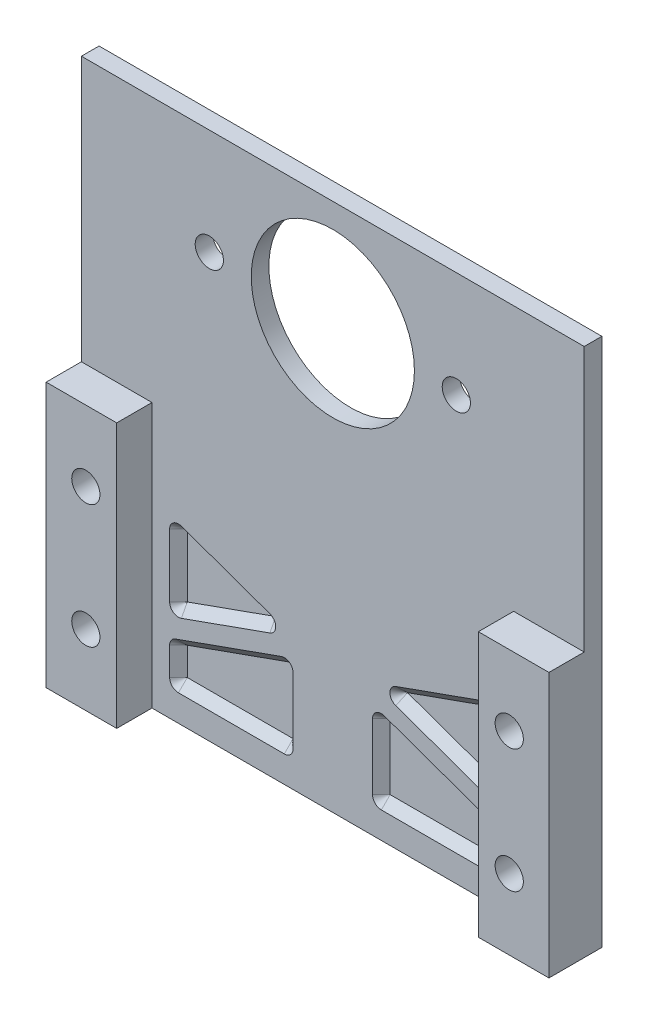
SolidWorks part; units mm, degrees
ref_plane "Ebene vorne" through (0, 0, 0) normal (0, 0, 1) x (1, 0, 0)
ref_plane "Ebene oben" through (0, 0, 0) normal (0, 1, 0) x (1, 0, 0)
ref_plane "Ebene rechts" through (0, 0, 0) normal (1, 0, 0) x (0, 0, -1)
sketch "Skizze1" plane through (0, 0, 0) normal (0, 0, 1) x (1, 0, 0)
  line L0 (0, 0) -> (0, 60) construction
  line L1 (28.5, 0) -> (-28.5, 0)
  line L2 (-28.5, 0) -> (-28.5, 60)
  line L3 (-28.5, 60) -> (28.5, 60)
  line L4 (28.5, 0) -> (28.5, 60)
  dimension "D1" = 57
  dimension "D2" = 60
extrude "Grundplatte" add sketch "Skizze1" along normal blind 2
sketch "Skizze2" plane through (0, 0, 2) normal (0, 0, 1) x (1, 0, 0)
  line L0 (0, 0) -> (0, 48) construction
  line L1 (14, 48) -> (-14, 48) construction
  line L2 (28.5, 60) -> (-28.5, 60) construction
  circle A0 centre (0, 48) radius 9.25
  circle A1 centre (-14, 48) radius 1.6
  circle A2 centre (14, 48) radius 1.6
  dimension "D2" = 18.5
  dimension "D3" = 3.2
  dimension "D1" = 12
  dimension "D4" = 28
extrude "Ausschnitt_Rolle" cut sketch "Skizze2" against normal through all
sketch "Skizze4" plane through (0, 0, 2) normal (0, 0, 1) x (1, 0, 0)
  line L0 (0, 60) -> (0, 0) construction
  line L1 (28.5, 60) -> (-28.5, 60) construction
  line L2 (20.5, 0) -> (20.5, 30)
  line L3 (-28.5, 0) -> (-20.5, 0)
  line L4 (-28.5, 0) -> (-28.5, 30)
  line L5 (-28.5, 30) -> (-20.5, 30)
  line L6 (-20.5, 0) -> (-20.5, 30)
  line L7 (28.5, 30) -> (20.5, 30)
  line L8 (28.5, 0) -> (28.5, 30)
  line L9 (28.5, 0) -> (20.5, 0)
  dimension "D1" = 8
  dimension "D2" = 30
extrude "Aufsatz Getriebe" add sketch "Skizze4" along normal blind 4
sketch "Skizze3" plane through (0, 0, 2) normal (0, 0, 1) x (1, 0, 0)
  line L0 (-24, 22) -> (-24, 8) construction
  line L1 (-24, 15) -> (24, 15) construction
  line L2 (0, 15) -> (0, 0) construction
  line L3 (-20.5, 0) -> (20.5, 0) construction
  line L4 (24, 22) -> (24, 8) construction
  line L5 (-20.5, 15) -> (-24, 15) construction
  line L6 (-20.5, 0) -> (-20.5, 30) construction
  circle A0 centre (-24, 22) radius 1.6
  circle A1 centre (-24, 8) radius 1.6
  circle A2 centre (24, 8) radius 1.6
  circle A3 centre (24, 22) radius 1.6
  dimension "D1" = 3.2
  dimension "D2" = 14
  dimension "D4" = 48
extrude "Bohrungen Getriebe" cut sketch "Skizze3" against normal through all from surface starting at face at (-24.5, 15, 6)
sketch "Skizze5" plane through (0, 0, 2) normal (0, 0, 1) x (1, 0, 0)
  line L0 (0, 60) -> (0, 0) construction
  line L1 (28.5, 60) -> (-28.5, 60) construction
  line L2 (-18.5, 20) -> (-18.5, 10)
  line L3 (-18.5, 10) -> (-4.5, 15)
  line L4 (-4.5, 15) -> (-18.5, 20)
  line L5 (-20.5, 15) -> (-18.5, 15) construction
  line L6 (-20.5, 0) -> (-20.5, 30) construction
  line L7 (-18.5, 15) -> (-4.5, 15) construction
  line L8 (-18.5, 7.8763) -> (-18.5, 3)
  line L9 (-18.5, 3) -> (-4.5, 3)
  line L10 (-4.5, 3) -> (-4.5, 12.8763)
  line L11 (-4.5, 12.8763) -> (-18.5, 7.8763)
  line L12 (-20.5, 0) -> (20.5, 0) construction
  line L13 (-20.5, 0) -> (-20.5, 30) construction
  line L14 (18.5, 15) -> (4.5, 15) construction
  line L15 (20.5, 15) -> (18.5, 15) construction
  line L16 (4.5, 12.8763) -> (18.5, 7.8763)
  line L17 (4.5, 3) -> (4.5, 12.8763)
  line L18 (18.5, 3) -> (4.5, 3)
  line L19 (18.5, 7.8763) -> (18.5, 3)
  line L20 (4.5, 15) -> (18.5, 20)
  line L21 (18.5, 10) -> (4.5, 15)
  line L22 (18.5, 20) -> (18.5, 10)
  dimension "D1" = 10
  dimension "D2" = 14
  dimension "D3" = 2
  dimension "D4" = 3
  dimension "D5" = 2
extrude "Schnitt-Linear austragen3" cut sketch "Skizze5" against normal offset from surface (1 mm away) 1 up to face at (22.4, 22, 0)
fillet "Verrundung1" radius 1 14 edges at (18.5, 20, 1.5) (18.5, 10, 1.5) (4.5, 15, 1.5) (4.5, 3, 1.5) (4.5, 12.8763, 1.5) (18.5, 7.8763, 1.5) (18.5, 3, 1.5) (-4.5, 3, 1.5) (-4.5, 12.8763, 1.5) (-4.5, 15, 1.5) (-18.5, 7.8763, 1.5) (-18.5, 3, 1.5) (-18.5, 10, 1.5) (-18.5, 20, 1.5)
chamfer "Fase1" distance 1 angle 45 28 edges at (4.924, 12.2747, 1) (11.8363, 10.2562, 1) (18.3174, 7.7476, 1) (18.5, 5.5858, 1) (18.2071, 3.2929, 1) (11.5, 3, 1) (4.7929, 3.2929, 1) (4.5, 7.7286, 1) (18.076, 10.6016, 1) (12.1503, 12.2678, 1) (6.4732, 15, 1) (12.1503, 17.7322, 1) (18.076, 19.3984, 1) (18.5, 15, 1) (-18.2071, 3.2929, 1) (-18.5, 5.5858, 1) (-18.3174, 7.7476, 1) (-11.8363, 10.2562, 1) (-4.924, 12.2747, 1) (-4.5, 7.7286, 1) (-4.7929, 3.2929, 1) (-11.5, 3, 1) (-18.076, 10.6016, 1) (-18.5, 15, 1) (-18.076, 19.3984, 1) (-12.1503, 17.7322, 1) (-6.4732, 15, 1) (-12.1503, 12.2678, 1)
